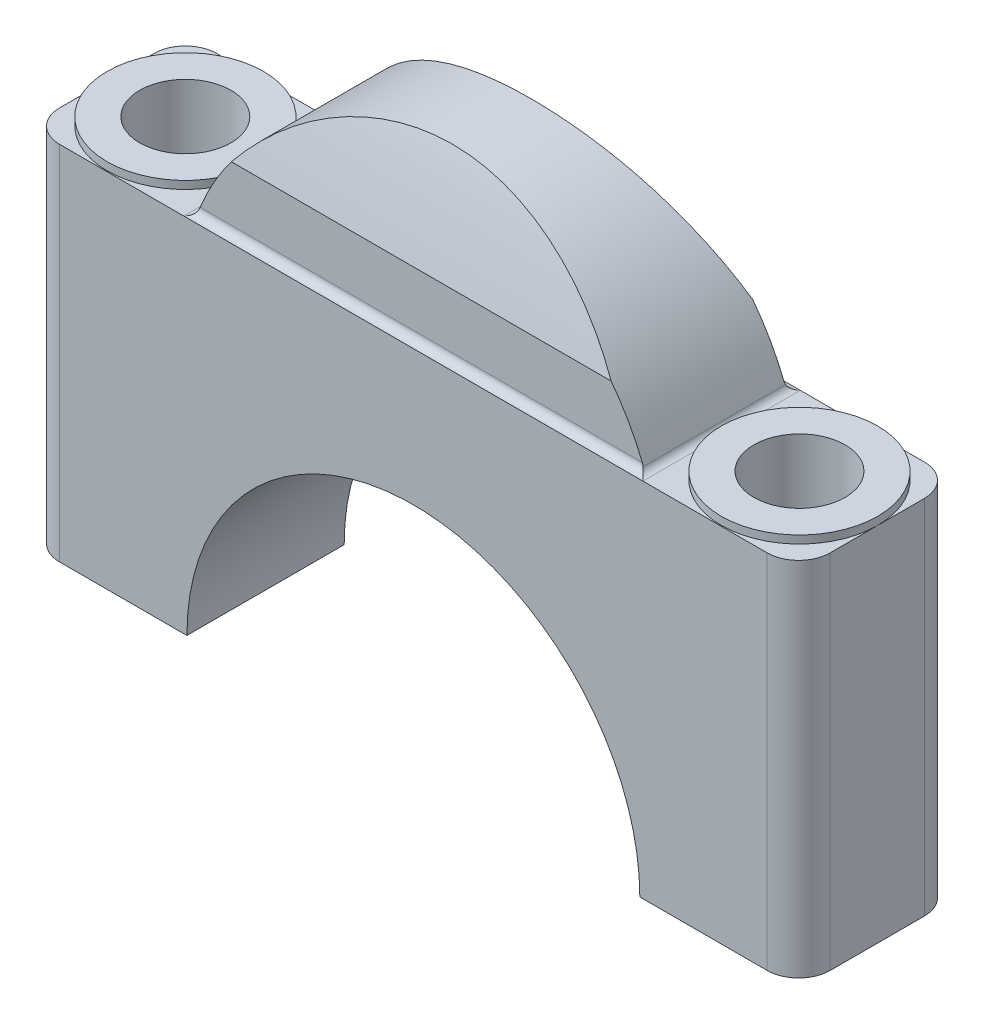
SolidWorks part; units mm, degrees
ref_plane "Alzado" through (0, 0, 0) normal (0, 0, 1) x (1, 0, 0)
ref_plane "Planta" through (0, 0, 0) normal (0, 1, 0) x (1, 0, 0)
ref_plane "Vista lateral" through (0, 0, 0) normal (1, 0, 0) x (0, 0, -1)
sketch "Croquis2" plane through (0, 0, 0) normal (0, 0, 1) x (1, 0, 0)
  line L0 (-49, 0) -> (-49, 46)
  line L1 (-49, 46) -> (49, 46)
  line L2 (49, 46) -> (49, 0)
  line L3 (49, 0) -> (28.8, 0)
  line L5 (-28.8, 0) -> (-49, 0)
  arc A0 (28.8, 0) -> (-28.8, 0) centre (0, 0) ccw
  dimension "D1" = 98
  dimension "D2" = 46
  dimension "D3" = 20.2
extrude "Saliente-Extruir2" add sketch "Croquis2" along normal mid plane 20
sketch "Croquis3" plane through (0, 46, 0) normal (0, 1, 0) x (1, 0, 0)
  line L0 (49, 10) -> (-49, 10) construction
  line L1 (49, -10) -> (49, 10) construction
  line L2 (-49, -10) -> (-49, 10) construction
  circle A0 centre (-39.0522, 0.0522) radius 9.9478
  circle A1 centre (39.0522, 0.0522) radius 9.9478
extrude "Saliente-Extruir3" add sketch "Croquis3" along normal blind 1
sketch "Croquis4" plane through (0, 46, 0) normal (0, 1, 0) x (1, 0, 0)
  circle A0 centre (-39.0522, 0.0522) radius 5.8
  circle A1 centre (39.0522, 0.0522) radius 5.8
  dimension "D1" = 11.6
extrude "Cortar-Extruir1" cut sketch "Croquis4" against normal through all both and the other way through all
sketch "Croquis5" plane through (0, 0, 0) normal (0, 0, 1) x (1, 0, 0)
  line L0 (-28.5, 46) -> (28.5, 46)
  line L1 (49, 46) -> (-49, 46) construction
  arc A1 (28.5, 46) -> (-28.5, 46) centre (0, 35.6938) ccw
  ellipse E0 centre (0, 46) end of major axis (28.5, 46) minor radius 20 construction
  dimension "D1" = 57
  dimension "D2" = 20
extrude "Saliente-Extruir4" add sketch "Croquis5" along normal mid plane 18
sketch "Croquis6" plane through (0, 0, 0) normal (1, 0, 0) x (0, 0, -1)
  line L0 (-9, 54) -> (9, 54)
  line L1 (-9, 66) -> (-9, 46) construction
  line L2 (9, 46) -> (9, 66) construction
  line L3 (-9, 46) -> (9, 46) construction
  line L4 (-9, 46) -> (9, 46) construction
  line L5 (-5, 66) -> (5, 66)
  line L6 (9, 66) -> (-9, 66) construction
  line L7 (-5, 66) -> (-9, 66)
  line L8 (-9, 66) -> (-9, 54)
  line L9 (9, 54) -> (9, 66)
  line L10 (9, 66) -> (5, 66)
  conic Q0 (-9, 54) -> (9, 54) control (0, 84.5595) rho 0.615447
  point P12 (0, 54)
  point P13 (0, 66)
  dimension "D1" = 8
  dimension "D2" = 10
extrude "Cortar-Extruir2" cut sketch "Croquis6" against normal through all both and the other way through all contours L8 Q0 L7 | L10 Q0 L9 region at (0, 62.0876, 7.7049) region at (0, 62.0876, -7.7049)
fillet "Redondeo3" radius 1 4 edges at (0, 46, -9) (28.5, 46, 0) (0, 46, 9) (-28.5, 46, 0)
fillet "Redondeo4" radius 4 4 edges at (49, 23, -10) (49, 23, 10) (-49, 23, -10) (-49, 23, 10)
